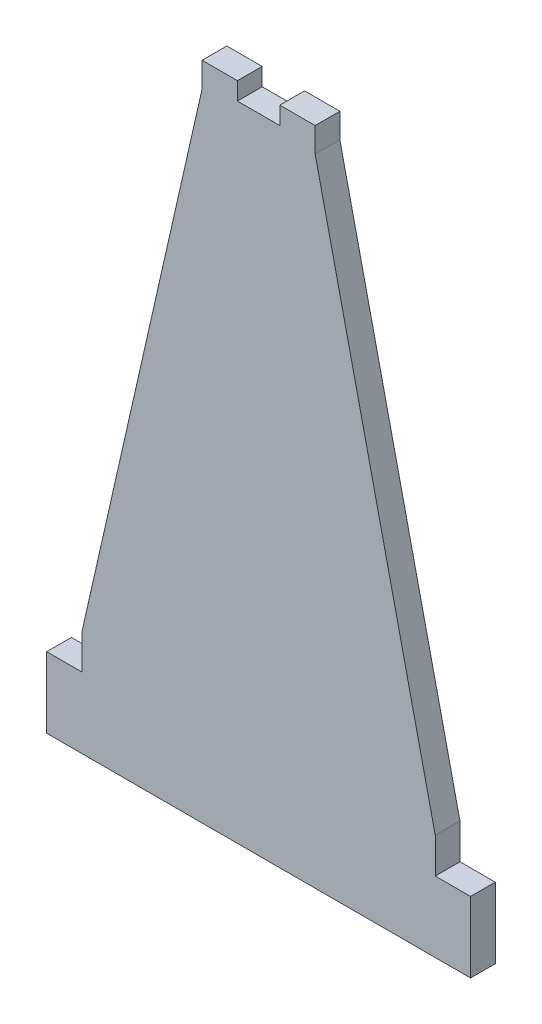
SolidWorks part; units mm, degrees
material "PBT General Purpose"
ref_plane "Front Plane" through (0, 0, 0) normal (0, 0, 1) x (1, 0, 0)
ref_plane "Top Plane" through (0, 0, 0) normal (0, 1, 0) x (1, 0, 0)
ref_plane "Right Plane" through (0, 0, 0) normal (1, 0, 0) x (0, 0, -1)
sketch "frame_outline" plane through (0, 0, 0) normal (0, 0, 1) x (1, 0, 0)
  line L110 (0, 0) -> (6, 0)
  line L117 (6, 0) -> (6, 1)
  line L118 (6, 1) -> (5.5, 1)
  line L119 (5.5, 1) -> (5.5, 1.5)
  line L120 (5.5, 1.5) -> (3.8, 9)
  line L121 (3.8, 9) -> (3.8, 9.35)
  line L122 (3.8, 9.35) -> (3.3, 9.35)
  line L123 (3.3, 9.35) -> (3.3, 9.1)
  line L124 (3.3, 9.1) -> (2.7, 9.1)
  line L125 (2.7, 9.1) -> (2.7, 9.35)
  line L126 (2.7, 9.35) -> (2.2, 9.35)
  line L127 (2.2, 9.35) -> (2.2, 9)
  line L128 (2.2, 9) -> (0.5, 1.5)
  line L129 (0.5, 1.5) -> (0.5, 1)
  line L130 (0.5, 1) -> (0, 1)
  line L131 (0, 1) -> (0, 0)
  line L132 (3, 9.1) -> (3, 0) construction
  dimension "D1" = 5
  dimension "D2" = 0.5
  dimension "D3" = 1
  dimension "D4" = 0.5
  dimension "D5" = 8
  dimension "D6" = 0.6
  dimension "D7" = 0.25
  dimension "D8" = 0.5
  dimension "D9" = 0.1
extrude "Boss-Extrude1" add sketch "frame_outline" along normal mid plane 0.35
equation "\"t\"= 0.25'thickness of the sheets"
equation "\"t_cf\"= 0.115'thickness of single carbon fiber layer"
equation "\"t_kapton\"= 0.025'thickness of single Kapton flex layer"
equation "\"t_fr4\"= 0.1'thickness of FR4 with copper layer"
equation "\"joint_flex\"= 0.1'Width of flextures gap"
equation "\"joint_flex_eff\"= 0.02'Width of flecture after castelation"
equation "\"joint_fold\"= 0.2'Width of folding joints for 90deg fold"
equation "\"gap_tolerance\"= 0.002'Width to have interfecence fit between carbon fiber inserts"
equation "\"assemble_angle\"= 90'Angle of assembly parts"
equation "\"D1@Boss-Extrude1\"=0.35"
equation "\"link_lift\"= 0.5'Actuation linkage amplification for the lift motion"
equation "\"link_swing\"= 0.45'Actuation linkage amplification for the swing motion"
